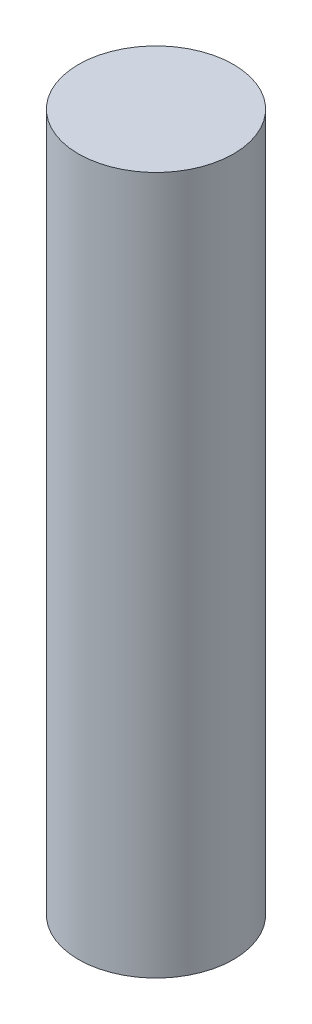
SolidWorks part; units mm, degrees
ref_plane "Ebene vorne" through (0, 0, 0) normal (0, 0, 1) x (1, 0, 0)
ref_plane "Ebene oben" through (0, 0, 0) normal (0, 1, 0) x (1, 0, 0)
ref_plane "Ebene rechts" through (0, 0, 0) normal (1, 0, 0) x (0, 0, -1)
sketch "Sketch1" plane through (0, 0, 0) normal (0, 0, 1) x (1, 0, 0)
  line L1 (0, 0) -> (-2, 0)
  line L2 (0, 0) -> (0, 18)
  line L3 (0, 18) -> (-2, 18)
  line L4 (-2, 0) -> (-2, 18)
  dimension "D1" = 2
  dimension "D2" = 18
revolve "Revolve1" add sketch "Sketch1" angle 360 about L2
